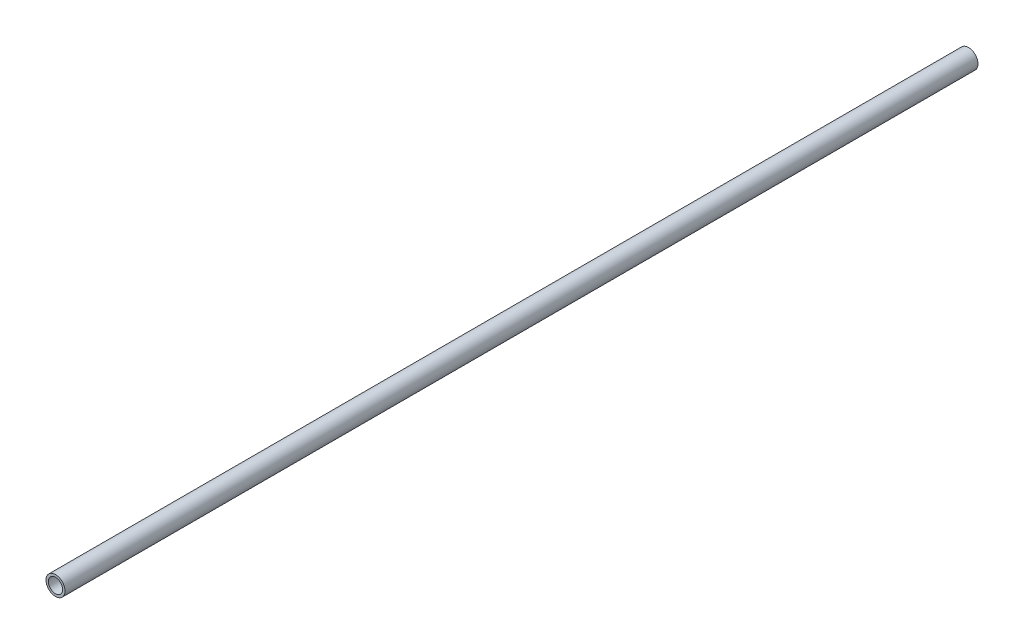
SolidWorks part; units mm, degrees
ref_plane "Front Plane" through (0, 0, 0) normal (0, 0, 1) x (1, 0, 0)
ref_plane "Top Plane" through (0, 0, 0) normal (0, 1, 0) x (1, 0, 0)
ref_plane "Right Plane" through (0, 0, 0) normal (1, 0, 0) x (0, 0, -1)
sketch "Sketch1" plane through (0, 0, 0) normal (0, 0, 1) x (1, 0, 0)
  circle A0 centre (0, 0) radius 9.525
  circle A1 centre (0, 0) radius 7.1438
  dimension "D1" = 19.05
  dimension "D2" = 14.2875
extrude "Boss-Extrude1" add sketch "Sketch1" along normal blind 914.4
equation "\"span\" = 48"
equation "\"wing_chord\"= 9"
equation "\"fuse_len\"= 15"
equation "\"fuse_height\"= 5"
equation "\"fuse_wid\"= 5"
equation "\"foam_t\"= 0.1875"
equation "\"main_spar_len\"= 36"
equation "\"D1@Boss-Extrude1\"= \"main_spar_len\""
